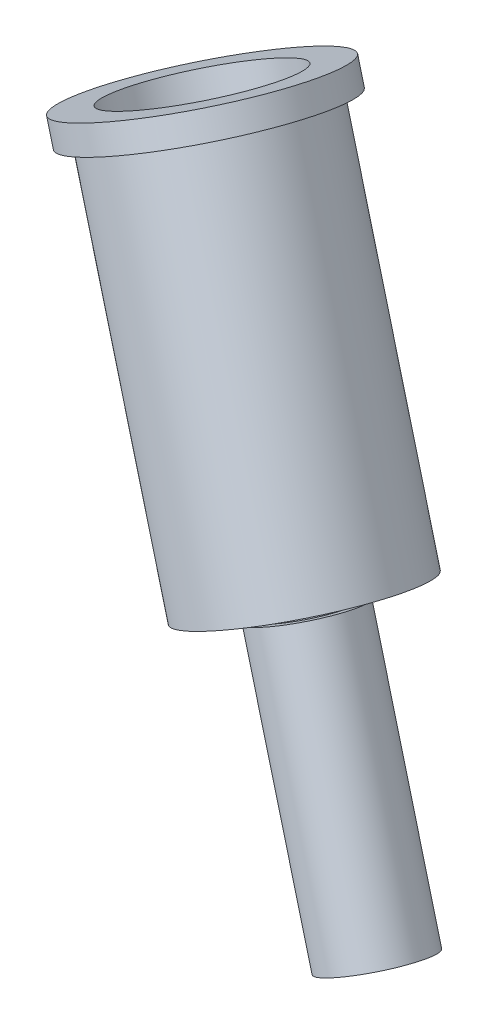
SolidWorks part; units mm, degrees
other "Markup1"
sketch "Sketch7" plane through (-206.0284, 201.4318, -3.7457) normal (-0.8382, 0.5448, -0.0267) x (0.4541, 0.7241, 0.5191)
ref_plane "Front Plane" through (0, 0, 0) normal (0, 0, 1) x (1, 0, 0)
ref_plane "Top Plane" through (0, 0, 0) normal (0, 1, 0) x (1, 0, 0)
ref_plane "Right Plane" through (0, 0, 0) normal (1, 0, 0) x (0, 0, -1)
sketch "Sketch1" plane through (-129.2035, 253.122, -50.2713) normal (-0.4477, 0.8771, -0.1742) x (0.8839, 0.4046, -0.2345)
  circle A0 centre (-31.0857, -28.5191) radius 11.43
  dimension "D1" = 22.86
extrude "Boss-Extrude1" add sketch "Sketch1" along normal blind 2.54 contours A0
sketch "Sketch2" plane through (-129.2035, 253.122, -50.2713) normal (0.4477, -0.8771, 0.1742) x (-0.8839, -0.4046, 0.2345)
  circle A0 centre (31.0857, -28.5191) radius 9.9949
  dimension "D1" = 19.9898
extrude "Boss-Extrude2" add sketch "Sketch2" along normal blind 35.56
sketch "Sketch3" plane through (-113.2837, 221.9337, -44.0772) normal (0.4477, -0.8771, 0.1742) x (-0.8839, -0.4046, 0.2345)
  line L0 (33.4658, -38.4046) -> (28.7055, -18.6336) construction
  circle A0 centre (31.0857, -28.5191) radius 3.81
  dimension "D1" = 7.62
extrude "Boss-Extrude3" add sketch "Sketch3" along normal blind 1.016 contours A0
sketch "Sketch4" plane through (-112.8289, 221.0426, -43.9002) normal (0.4477, -0.8771, 0.1742) x (-0.8839, -0.4046, 0.2345)
  line L0 (39.2348, -26.557) -> (22.9365, -30.4812) construction
  circle A0 centre (31.0857, -28.5191) radius 4.7625
  dimension "D1" = 9.525
extrude "Boss-Extrude4" add sketch "Sketch4" along normal blind 26.0282 contours A0
sketch "Sketch5" plane through (-130.3406, 255.3497, -50.7138) normal (-0.4477, 0.8771, -0.1742) x (0.8839, 0.4046, -0.2345)
  line L0 (-33.4658, -38.4046) -> (-28.7055, -18.6336) construction
  circle A0 centre (-31.0857, -28.5191) radius 3.175
  dimension "D1" = 6.35
extrude "Cut-Extrude1" cut sketch "Sketch5" against normal through all
sketch "Sketch6" plane through (-130.3406, 255.3497, -50.7138) normal (-0.4477, 0.8771, -0.1742) x (0.8839, 0.4046, -0.2345)
  circle A0 centre (-31.0857, -28.5191) radius 7.9375
  dimension "D1" = 15.875
extrude "Cut-Extrude2" cut sketch "Sketch6" against normal blind 22.86
